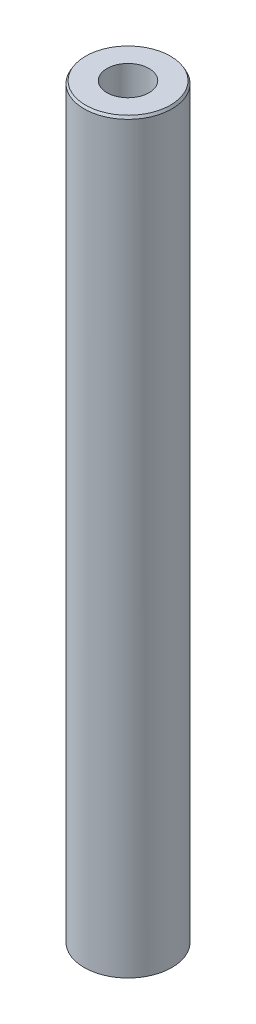
SolidWorks part; units mm, degrees
ref_plane "Front Plane" through (0, 0, 0) normal (0, 0, 1) x (1, 0, 0)
ref_plane "Top Plane" through (0, 0, 0) normal (0, 1, 0) x (1, 0, 0)
ref_plane "Right Plane" through (0, 0, 0) normal (1, 0, 0) x (0, 0, -1)
sketch "Sketch1" plane through (0, 0, 0) normal (0, 1, 0) x (1, 0, 0)
  circle A0 centre (0, 0) radius 12.5
  dimension "SHAFT_OD" = 25
extrude "Boss-Extrude1" add sketch "Sketch1" along normal blind 212.8741
sketch "Sketch2" plane through (0, 0, 0) normal (0, 1, 0) x (1, 0, 0)
  circle A0 centre (0, 0) radius 5.9892
  dimension "BORE_D" = 11.9783
extrude "Cut-Extrude1" cut sketch "Sketch2" along normal through all
chamfer "Chamfer1" distance 0.7198 angle 30 2 edges at (0, 212.8741, 12.5) (0, 0, 12.5) first distance on face at (0, 212.8741, 12.5) first distance on face at (0, 0, 5.9892)
